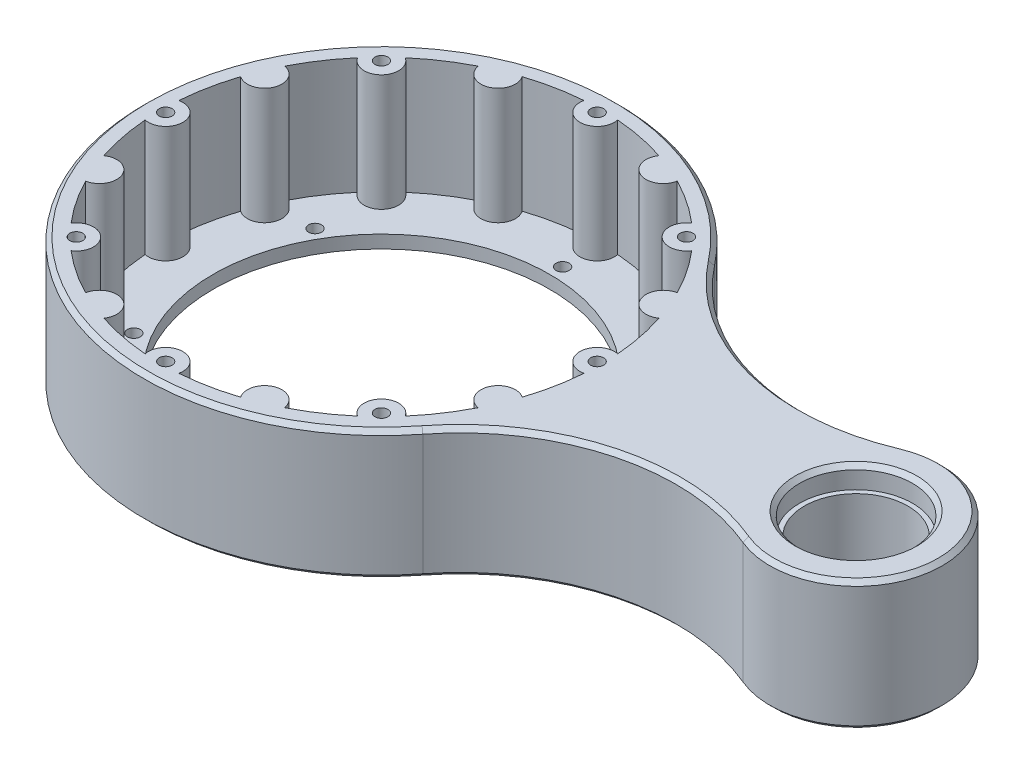
SolidWorks part; units mm, degrees
ref_plane "Front Plane" through (0, 0, 0) normal (0, 0, 1) x (1, 0, 0)
ref_plane "Top Plane" through (0, 0, 0) normal (0, 1, 0) x (1, 0, 0)
ref_plane "Right Plane" through (0, 0, 0) normal (1, 0, 0) x (0, 0, -1)
sketch "Sketch1" plane through (0, 0, 0) normal (0, 1, 0) x (1, 0, 0)
  circle A0 centre (0, 0) radius 39
  circle A1 centre (0, 0) radius 55
  circle A2 centre (0, 50) radius 1.5
  circle A3 centre (35.3553, 35.3553) radius 1.5
  circle A4 centre (50, 0) radius 1.5
  circle A5 centre (35.3553, -35.3553) radius 1.5
  circle A6 centre (0, -50) radius 1.5
  circle A7 centre (-35.3553, -35.3553) radius 1.5
  circle A8 centre (-50, 0) radius 1.5
  circle A9 centre (-35.3553, 35.3553) radius 1.5
  circle A18 centre (0, 42) radius 1.5
  circle A19 centre (36.3731, 21) radius 1.5
  circle A20 centre (36.3731, -21) radius 1.5
  circle A21 centre (0, -42) radius 1.5
  circle A22 centre (-36.3731, -21) radius 1.5
  circle A23 centre (-36.3731, 21) radius 1.5
  point P22 (0, 0)
  point P35 (0, 0)
  point P39 (0, 0)
  dimension "D1" = 110
  dimension "D2" = 78
  dimension "D3" = 3
  dimension "D6" = 42
  dimension "D7" = 3
  dimension "D4" = 50
  dimension "D5" = 8
  dimension "D8" = 6
extrude "Boss-Extrude1" add sketch "Sketch1" along normal blind 3
sketch "Sketch2" plane through (0, 3, 0) normal (0, 1, 0) x (1, 0, 0)
  arc A0 (-3.9086, 50.85) -> (3.9086, 50.85) centre (0, 50) ccw
  arc A1 (15.8483, 48.475) -> (23.0706, 45.4835) centre (19.1342, 46.194) ccw
  arc A2 (33.1926, 38.7202) -> (38.7202, 33.1926) centre (35.3553, 35.3553) ccw
  arc A3 (45.4835, 23.0706) -> (48.475, 15.8483) centre (46.194, 19.1342) ccw
  arc A4 (50.85, 3.9086) -> (50.85, -3.9086) centre (50, 0) ccw
  arc A5 (48.475, -15.8483) -> (45.4835, -23.0706) centre (46.194, -19.1342) ccw
  arc A6 (38.7202, -33.1926) -> (33.1926, -38.7202) centre (35.3553, -35.3553) ccw
  arc A7 (23.0706, -45.4835) -> (15.8483, -48.475) centre (19.1342, -46.194) ccw
  arc A8 (3.9086, -50.85) -> (-3.9086, -50.85) centre (0, -50) ccw
  arc A9 (-15.8483, -48.475) -> (-23.0706, -45.4835) centre (-19.1342, -46.194) ccw
  arc A10 (-33.1926, -38.7202) -> (-38.7202, -33.1926) centre (-35.3553, -35.3553) ccw
  arc A11 (-45.4835, -23.0706) -> (-48.475, -15.8483) centre (-46.194, -19.1342) ccw
  arc A12 (-50.85, -3.9086) -> (-50.85, 3.9086) centre (-50, 0) ccw
  arc A13 (-48.475, 15.8483) -> (-45.4835, 23.0706) centre (-46.194, 19.1342) ccw
  arc A14 (-38.7202, 33.1926) -> (-33.1926, 38.7202) centre (-35.3553, 35.3553) ccw
  arc A15 (-23.0706, 45.4835) -> (-15.8483, 48.475) centre (-19.1342, 46.194) ccw
  arc A16 (-48.475, 15.8483) -> (-50.85, 3.9086) centre (0, 0) ccw
  arc A17 (-50.85, -3.9086) -> (-48.475, -15.8483) centre (0, 0) ccw
  arc A18 (-45.4835, -23.0706) -> (-38.7202, -33.1926) centre (0, 0) ccw
  arc A19 (-33.1926, -38.7202) -> (-23.0706, -45.4835) centre (0, 0) ccw
  arc A20 (-15.8483, -48.475) -> (-3.9086, -50.85) centre (0, 0) ccw
  arc A21 (3.9086, -50.85) -> (15.8483, -48.475) centre (0, 0) ccw
  arc A22 (23.0706, -45.4835) -> (33.1926, -38.7202) centre (0, 0) ccw
  arc A23 (38.7202, -33.1926) -> (45.4835, -23.0706) centre (0, 0) ccw
  arc A24 (48.475, -15.8483) -> (50.85, -3.9086) centre (0, 0) ccw
  arc A25 (50.85, 3.9086) -> (48.475, 15.8483) centre (0, 0) ccw
  arc A26 (45.4835, 23.0706) -> (38.7202, 33.1926) centre (0, 0) ccw
  arc A27 (33.1926, 38.7202) -> (23.0706, 45.4835) centre (0, 0) ccw
  arc A28 (15.8483, 48.475) -> (3.9086, 50.85) centre (0, 0) ccw
  arc A29 (-3.9086, 50.85) -> (-15.8483, 48.475) centre (0, 0) ccw
  arc A30 (-23.0706, 45.4835) -> (-33.1926, 38.7202) centre (0, 0) ccw
  arc A31 (-38.7202, 33.1926) -> (-45.4835, 23.0706) centre (0, 0) ccw
  circle A32 centre (0, 0) radius 55 construction
  circle A33 centre (0, 0) radius 55
  circle A34 centre (-35.3553, 35.3553) radius 1.5 construction
  circle A35 centre (-50, 0) radius 1.5 construction
  circle A36 centre (-35.3553, -35.3553) radius 1.5 construction
  circle A37 centre (0, -50) radius 1.5 construction
  circle A38 centre (35.3553, -35.3553) radius 1.5 construction
  circle A39 centre (50, 0) radius 1.5 construction
  circle A40 centre (35.3553, 35.3553) radius 1.5 construction
  circle A41 centre (0, 50) radius 1.5 construction
  circle A42 centre (-35.3553, 35.3553) radius 1.5
  circle A43 centre (-50, 0) radius 1.5
  circle A44 centre (-35.3553, -35.3553) radius 1.5
  circle A45 centre (0, -50) radius 1.5
  circle A46 centre (35.3553, -35.3553) radius 1.5
  circle A47 centre (50, 0) radius 1.5
  circle A48 centre (35.3553, 35.3553) radius 1.5
  circle A49 centre (0, 50) radius 1.5
  point P35 (0, 0)
  dimension "D1" = 8
  dimension "D4" = 102
  dimension "D2" = 50
  dimension "D3" = 16
extrude "Boss-Extrude3" add sketch "Sketch2" along normal blind 27
sketch "Sketch3" plane through (0, 30, 0) normal (0, 1, 0) x (1, 0, 0)
  circle A0 centre (0, 0) radius 55 construction
  arc A1 (43.3929, -33.7944) -> (43.3929, 33.7944) centre (0, 0) ccw
  arc A5 (102.2403, -18.4333) -> (102.2403, 18.4333) centre (110, 0) ccw
  circle A6 centre (110, 0) radius 13.1
  arc A7 (43.3929, -33.7944) -> (102.2403, -18.4333) centre (82.8409, -64.5165) cw
  arc A8 (43.3929, 33.7944) -> (102.2403, 18.4333) centre (82.8409, 64.5165) ccw
  dimension "D1" = 40
  dimension "D4" = 50
  dimension "D2" = 26.2
  dimension "D5" = 50
  dimension "D3" = 110
extrude "Boss-Extrude4" add sketch "Sketch3" along normal blind 30 from surface starting at face at (0, 0, 55)
sketch "Sketch6" plane through (0, 30, 0) normal (0, 1, 0) x (1, 0, 0)
  circle A0 centre (110, 0) radius 12
  circle A1 centre (110, 0) radius 13.1 construction
  circle A2 centre (110, 0) radius 13.1
  dimension "D1" = 24
extrude "Boss-Extrude5" add sketch "Sketch6" against normal blind 20 from offset 5 offset against normal yes
chamfer "Chamfer1" distance 1 angle 45 10 edges at (110, 0, 13.1) (110, 30, 13.1) (70.2124, 0, -16.1376) (130, 0, 0) (70.2124, 0, 16.1376) (70.2124, 30, -16.1376) (130, 30, 0) (70.2124, 30, 16.1376) (-55, 0, 0) (-55, 30, 0)
